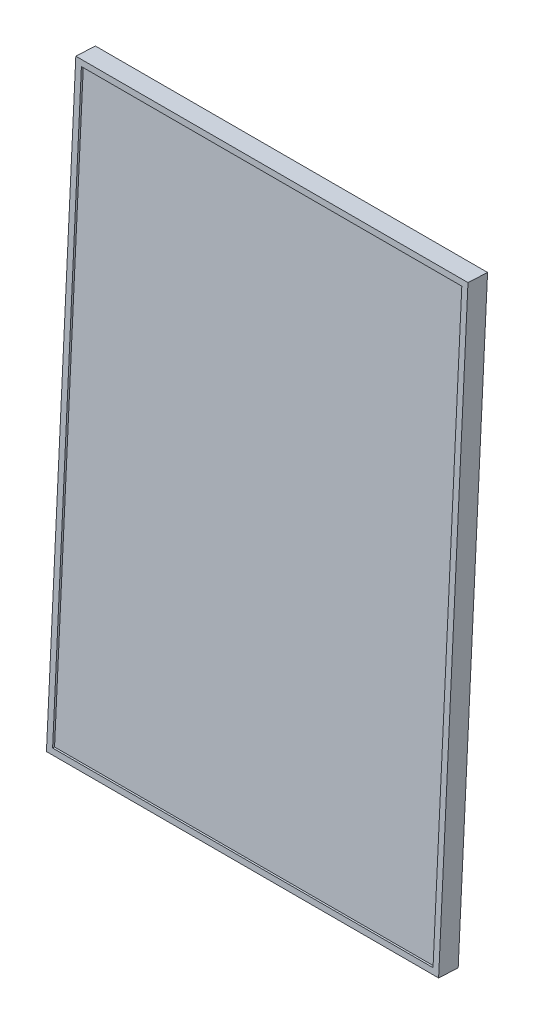
SolidWorks part; units mm, degrees
ref_plane "Front Plane" through (0, 0, 0) normal (0, 0, 1) x (1, 0, 0)
ref_plane "Top Plane" through (0, 0, 0) normal (0, 1, 0) x (1, 0, 0)
ref_plane "Right Plane" through (0, 0, 0) normal (1, 0, 0) x (0, 0, -1)
sketch "Sketch2" plane through (0, 3.0304, 60.6083) normal (0, 0.0499, 0.9988) x (1, 0, 0)
  line L1 (-96.0427, 14.2431) -> (103.9573, 14.2431)
  line L2 (-96.0427, 14.2431) -> (-96.0427, -285.7569)
  line L3 (-96.0427, -285.7569) -> (103.9573, -285.7569)
  line L4 (103.9573, 14.2431) -> (103.9573, -285.7569)
  line L6 (3.9573, 14.2431) -> (3.9573, -285.7569) construction
  dimension "D1" = 200
  dimension "D2" = 300
extrude "Boss-Extrude1" add sketch "Sketch2" along normal blind 5 and the other way blind 5
ref_plane "Plane1" through (-259.928, 371.6616, -7.1133) normal (0, 1, 0) x (1, 0, 0)
sketch "Sketch4" plane through (0, 3.2801, 65.602) normal (0, 0.0499, 0.9988) x (1, 0, 0)
  line L0 (-96.0427, -285.7569) -> (103.9573, -285.7569) construction
  line L1 (100.9573, -282.7569) -> (-93.0427, -282.7569)
  line L2 (100.9573, -282.7569) -> (100.9573, 11.2431)
  line L3 (100.9573, 11.2431) -> (-93.0427, 11.2431)
  line L4 (-93.0427, -282.7569) -> (-93.0427, 11.2431)
  line L5 (103.9573, -285.7569) -> (103.9573, 14.2431) construction
  line L6 (-96.0427, 14.2431) -> (-96.0427, -285.7569) construction
  line L7 (103.9573, 14.2431) -> (-96.0427, 14.2431) construction
  dimension "D1" = 3
  dimension "D2" = 3
  dimension "D3" = 3
  dimension "D4" = 3
extrude "Cut-Extrude1" cut sketch "Sketch4" against normal blind 1
sketch "Sketch5" plane through (0, 3.2302, 64.6033) normal (0, 0.0499, 0.9988) x (1, 0, 0)
  line L0 (-17.1208, -317.4296) -> (271.5459, -317.4296) construction
